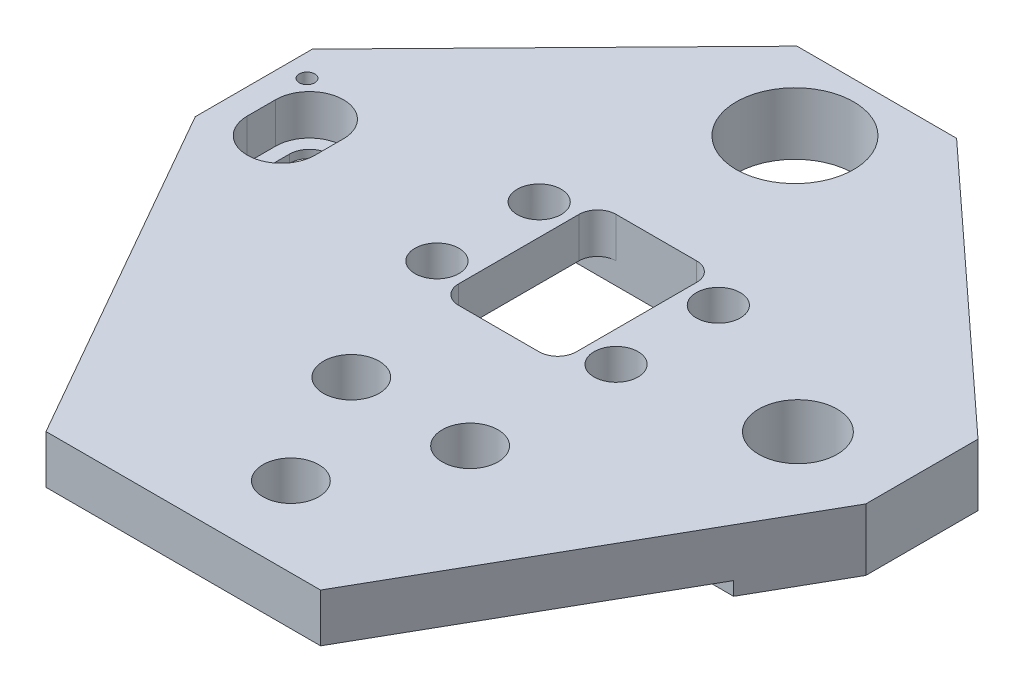
SolidWorks part; units mm, degrees
material "1060 Alloy"
ref_plane "Front Plane" through (0, 0, 0) normal (0, 0, 1) x (1, 0, 0)
ref_plane "Top Plane" through (0, 0, 0) normal (0, 1, 0) x (1, 0, 0)
ref_plane "Right Plane" through (0, 0, 0) normal (1, 0, 0) x (0, 0, -1)
sketch "Sketch1" plane through (0, 0, 0) normal (0, 1, 0) x (1, 0, 0)
  line L0 (0, 0) -> (0, -56.0308) construction
  line L1 (0, 0) -> (54.1, 0) construction
  line L2 (54.1, 18.1) -> (54.1, 0)
  line L3 (54.1, 18.1) -> (10.3345, 58.4092)
  line L4 (10.3345, 58.4092) -> (-15.4155, 58.4092)
  line L5 (-15.4155, 58.4092) -> (-54.1, 18.8922)
  line L6 (-54.1, 18.8922) -> (-54.1, 0)
  line L7 (-54.1, 0) -> (-22.15, -56.0308)
  line L8 (-22.15, -56.0308) -> (22.15, -56.0308)
  line L9 (22.15, -56.0308) -> (54.1, 0)
  line L11 (-9.5, 20.3092) -> (9.5, 20.3092)
  line L12 (-9.5, 20.3092) -> (-9.5, -5.1108)
  line L13 (-9.5, -5.1108) -> (9.5, -5.1108)
  line L14 (9.5, 20.3092) -> (9.5, -5.1108)
  dimension "D1" = 108.2
  dimension "D2" = 50.92
  dimension "D3" = 25.75
  dimension "D4" = 64.5
  dimension "D5" = 18.1
  dimension "D6" = 59.5
  dimension "D7" = 44.3
  dimension "D8" = 55.3
  dimension "D9" = 38.1
  dimension "D10" = 19
  dimension "D11" = 44.6
  dimension "D12" = 25.42
extrude "Boss-Extrude2" add sketch "Sketch1" along normal blind 10
fillet "Fillet1" radius 3 4 edges at (-9.5, 5, 5.1108) (9.5, 5, 5.1108) (9.5, 5, -20.3092) (-9.5, 5, -20.3092)
sketch "Sketch3" plane through (0, 0, -58.4092) normal (0, 0, -1) x (-1, 0, 0)
  line L0 (-10.3345, 0) -> (15.4155, 0) construction
  line L1 (54.1, 0) -> (35, 0)
  line L2 (54.1, 0) -> (54.1, 2.2)
  line L3 (54.1, 2.2) -> (35, 2.2)
  line L4 (35, 0) -> (35, 2.2)
  line L5 (54.1, 10) -> (54.1, 0) construction
  line L6 (-10.3345, 10) -> (15.4155, 10) construction
  dimension "D1" = 7.8
  dimension "D2" = 19.1
extrude "Cut-Extrude2" cut sketch "Sketch3" against normal through all
sketch "Sketch4" plane through (0, 10, 0) normal (0, 1, 0) x (1, 0, 0)
  line L0 (0, 20.3092) -> (0, -5.1108) construction
  line L1 (6.5, 20.3092) -> (-6.5, 20.3092) construction
  line L2 (-6.5, -5.1108) -> (6.5, -5.1108) construction
  line L3 (-14.45, 7.5992) -> (14.45, 7.5992) construction
  line L4 (-44.53, 8.8692) -> (-44.53, 4.2892) construction
  line L5 (-39.06, 8.8692) -> (-39.06, 4.2892)
  line L6 (-50, 8.8692) -> (-50, 4.2892)
  line L7 (4.48, -43.1508) -> (4.48, -31.1076) construction
  line L8 (-5.105, -23.8162) -> (4.48, -31.1076) construction
  line L9 (-5.105, -23.8162) -> (4.48, -43.1508) construction
  line L10 (-5.105, -23.8162) -> (14.065, -23.8162) construction
  line L11 (57.39, 62.1092) -> (57.39, -55.0587) construction
  line L12 (-3.065, 45.7342) -> (6.41, 45.7342) construction
  line L13 (9.5, -2.1108) -> (9.5, 17.3092) construction
  line L14 (-3.065, 45.7342) -> (-3.065, 55.2092) construction
  line L16 (-3.065, 36.2592) -> (-3.065, 20.3092) construction
  line L19 (38.535, 4.6092) -> (44.865, 4.6092) construction
  line L21 (57.39, 62.1092) -> (-64.0899, 62.1092) construction
  line L22 (38.535, 4.6092) -> (38.535, 10.9392) construction
  line L23 (-44.53, 14.3392) -> (-44.53, -1.1808) construction
  line L24 (-14.45, -0.6508) -> (-14.45, 15.8492) construction
  line L25 (14.45, -0.6508) -> (14.45, 15.8492) construction
  circle A0 centre (38.535, 4.6092) radius 6.33
  circle A1 centre (-14.45, -0.6508) radius 3.55
  circle A2 centre (-14.45, 15.8492) radius 3.55
  circle A3 centre (14.45, -0.6508) radius 3.55
  circle A4 centre (14.45, 15.8492) radius 3.55
  circle A5 centre (-5.105, -23.8162) radius 4.5
  circle A6 centre (14.065, -23.8162) radius 4.5
  circle A7 centre (4.48, -43.1508) radius 4.5
  circle A8 centre (4.48, -31.1076) radius 1.875
  arc A9 (-39.06, 8.8692) -> (-50, 8.8692) centre (-44.53, 8.8692) ccw
  arc A10 (-50, 4.2892) -> (-39.06, 4.2892) centre (-44.53, 4.2892) ccw
  circle A11 centre (-3.065, 45.7342) radius 9.475
  circle A12 centre (-50.45, 14.3792) radius 1.25
  circle A13 centre (38.535, 4.6092) radius 7.945 construction
  point P28 (-44.53, 6.5792)
  dimension "D1" = 9
  dimension "D5" = 12.66
  dimension "D10" = 18.95
  dimension "D18" = 3.75
  dimension "D21" = 7.1
  dimension "D22" = 2.5
  dimension "D2" = 19.17
  dimension "D3" = 21.58
  dimension "D4" = 38.04
  dimension "D7" = 47.89
  dimension "D8" = 52.91
  dimension "D9" = 50.98
  dimension "D11" = 15.95
  dimension "D12" = 6.9
  dimension "D14" = 10.94
  dimension "D15" = 59.5
  dimension "D16" = 15.52
  dimension "D17" = 47.77
  dimension "D19" = 28.9
  dimension "D20" = 16.5
  dimension "D23" = 59.95
  dimension "D24" = 7.8
extrude "Cut-Extrude3" cut sketch "Sketch4" against normal through all contours A11 | A6 | A5 | A7 | A0 | A4 | A3 | A1 | A2 | A12 region at (38.535, 10, -4.6092) region at (-14.45, 10, 0.6508) region at (-14.45, 10, -15.8492) region at (14.45, 10, 0.6508) region at (14.45, 10, -15.8492) region at (-5.105, 10, 23.8162) region at (14.065, 10, 23.8162) region at (4.48, 10, 43.1508) region at (-3.065, 10, -45.7342) region at (-50.45, 10, -14.3792)
sketch "Sketch5" plane through (-35, 0, 0) normal (-1, 0, 0) x (0, 0, 1)
  line L0 (33.4957, 2.2) -> (-38.4032, 2.2) construction
  line L1 (13.5908, 2.2) -> (56.0308, 2.2)
  line L2 (13.5908, 2.2) -> (13.5908, 0)
  line L3 (13.5908, 0) -> (56.0308, 0)
  line L4 (56.0308, 2.2) -> (56.0308, 0)
  line L5 (-58.4092, 10) -> (-58.4092, 0) construction
  line L6 (33.4957, 0) -> (-38.4032, 0) construction
  line L7 (56.0308, 10) -> (56.0308, 0) construction
  dimension "D1" = 72
extrude "Cut-Extrude4" cut sketch "Sketch5" against normal through all
sketch "Sketch6" plane through (0, 0, 0) normal (0, -1, 0) x (1, 0, 0)
  line L0 (-6.5, 5.1108) -> (6.5, 5.1108) construction
  line L1 (19.695, -20.3092) -> (-19.695, -20.3092)
  line L2 (19.695, -20.3092) -> (19.695, 5.1108)
  line L3 (19.695, 5.1108) -> (-19.695, 5.1108)
  line L4 (-19.695, -20.3092) -> (-19.695, 5.1108)
  line L5 (6.5, -20.3092) -> (-6.5, -20.3092) construction
  line L6 (0, 5.1108) -> (0, -20.3092) construction
  line L7 (9.5, 2.1108) -> (9.5, -17.3092) construction
  line L8 (-9.5, -17.3092) -> (-9.5, 2.1108) construction
  dimension "D1" = 39.39
extrude "Cut-Extrude5" cut sketch "Sketch6" against normal blind 3.5
fillet "Fillet2" radius 2 4 edges at (19.695, 1.75, 5.1108) (19.695, 1.75, -20.3092) (-19.695, 1.75, 5.1108) (-19.695, 1.75, -20.3092)
extrude "Cut-Extrude6" cut sketch "Sketch4<3>" against normal blind 6.5 contours L6 A10 L5 A9 region at (-44.53, 10, -6.5792)
sketch "Sketch4<3>" plane through (0, 10, 0) normal (0, 1, 0) x (1, 0, 0) same geometry as "Sketch4"
sketch "Sketch7" plane through (0, 3.5, 0) normal (0, 1, 0) x (-1, 0, 0)
  line L0 (44.53, -8.8692) -> (44.53, -4.2892) construction
  line L1 (41.28, -8.8692) -> (41.28, -4.2892)
  line L2 (47.78, -8.8692) -> (47.78, -4.2892)
  arc A0 (41.28, -8.8692) -> (47.78, -8.8692) centre (44.53, -8.8692) ccw
  arc A1 (47.78, -4.2892) -> (41.28, -4.2892) centre (44.53, -4.2892) ccw
  arc A2 (39.06, -8.8692) -> (50, -8.8692) centre (44.53, -8.8692) ccw construction
  arc A3 (50, -4.2892) -> (39.06, -4.2892) centre (44.53, -4.2892) ccw construction
  point P2 (44.53, -6.5792)
  dimension "D1" = 6.5
extrude "Cut-Extrude7" cut sketch "Sketch7" against normal through all
